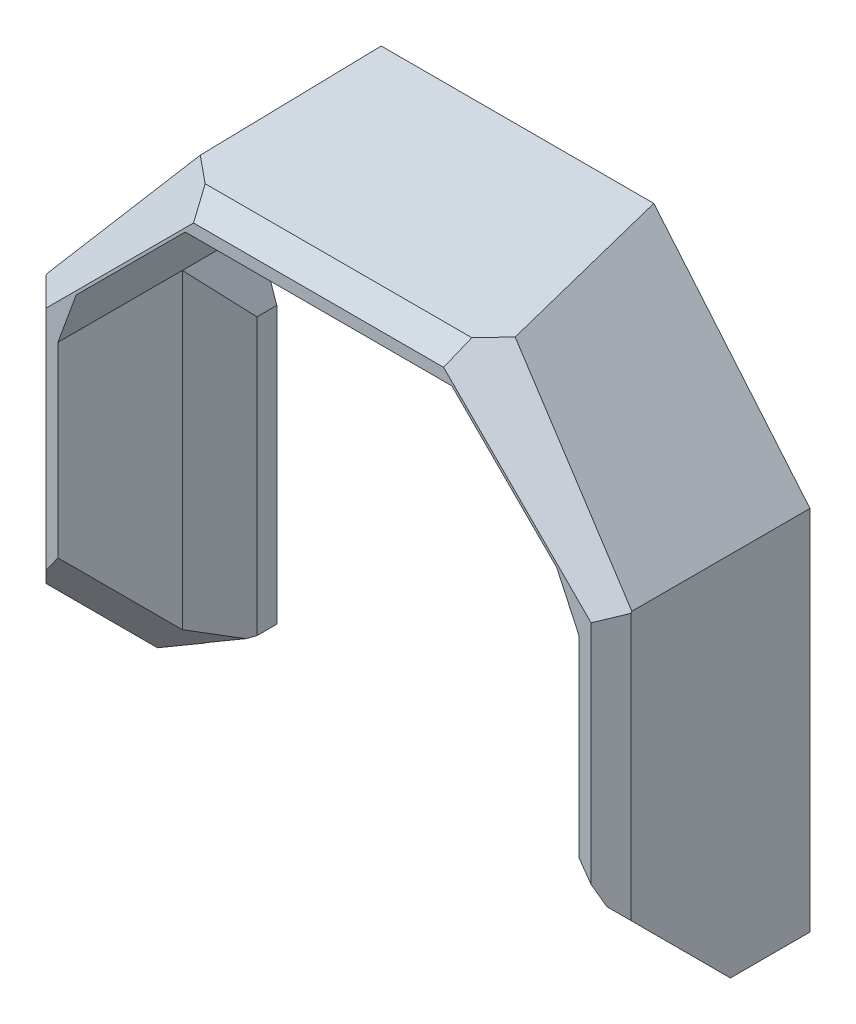
SolidWorks part; units mm, degrees
ref_plane "Спереди" through (0, 0, 0) normal (0, 0, 1) x (1, 0, 0)
ref_plane "Сверху" through (0, 0, 0) normal (0, 1, 0) x (1, 0, 0)
ref_plane "Справа" through (0, 0, 0) normal (1, 0, 0) x (0, 0, -1)
sketch "Эскиз1" plane through (0, 0, 0) normal (0, 0, 1) x (1, 0, 0)
  line L1 (-219.5225, 143.3263) -> (-117.1187, 143.3263)
  line L2 (-219.5225, 143.3263) -> (-219.5225, 57.8985)
  line L3 (-219.5225, 57.8985) -> (-117.1187, 57.8985)
  line L4 (-117.1187, 143.3263) -> (-117.1187, 57.8985)
sketch "Эскиз2" plane through (0, 0, 0) normal (0, 0, 1) x (1, 0, 0)
  line L12 (-163.3228, 250.3915) -> (-163.3228, -14.5346) construction
  line L14 (-228.8228, 61.4013) -> (-228.8228, 153.4013)
  line L15 (-228.8228, 153.4013) -> (-196.8228, 185.4013)
  line L16 (-196.8228, 185.4013) -> (-129.8228, 185.4013)
  line L17 (-129.8228, 185.4013) -> (-97.8228, 153.4013)
  line L18 (-97.8228, 153.4013) -> (-97.8228, 61.5309)
  line L19 (-252.6709, 153.4013) -> (-72.6741, 153.4013) construction
  line L20 (-97.8228, 61.5309) -> (-89.8228, 61.5309)
  line L21 (-89.8228, 61.5309) -> (-89.8228, 153.4013)
  line L22 (-89.8228, 153.4013) -> (-129.8228, 193.4013)
  line L23 (-129.8228, 193.4013) -> (-196.8228, 193.4013)
  line L24 (-196.8228, 193.4013) -> (-236.8228, 153.4013)
  line L25 (-236.8228, 153.4013) -> (-236.8228, 61.4013)
  line L26 (-236.8228, 61.4013) -> (-228.8228, 61.4013)
  line L27 (-196.8228, 216.9367) -> (-196.8228, 161.6417) construction
  line L28 (-129.8228, 216.9367) -> (-129.8228, 161.6417) construction
  point P5 (-163.3228, 185.4013)
  point P19 (0, 0)
  point P22 (0, 0)
  point P25 (0, 0)
  point P26 (0, 0)
  dimension "D1" = 135
  dimension "D2" = 135
  dimension "D3" = 67
  dimension "D4" = 92
  dimension "D5" = 32
  dimension "D6" = 8
extrude "Бобышка-Вытянуть2" add sketch "Эскиз2" along normal blind 50
chamfer "Фаска1" distance 30 angle 45 2 edges at (-232.8228, 61.4013, 50) (-93.8228, 61.5309, 50)
chamfer "Фаска2" distance 5 angle 45 5 edges at (-236.8228, 122.4013, 50) (-216.8228, 173.4013, 50) (-89.8228, 122.4661, 50) (-109.8228, 173.4013, 50) (-163.3228, 193.4013, 50)
chamfer "Фаска3" distance 5 angle 45 2 edges at (-97.8228, 76.5309, 35) (-228.8228, 76.4013, 35)
ref_plane "Плоскость4" through (-129.8228, 0, 0) normal (1, 0, 0) x (0, 0, -1)
sketch "Эскиз3" plane through (-129.8228, 0, 0) normal (1, 0, 0) x (0, 0, -1)
  line L0 (-45, 193.4013) -> (0, 193.4013)
  line L1 (0, 193.4013) -> (0, 200.5043)
  line L2 (0, 260.3915) -> (0, -1249.6085) construction
  line L3 (0, 200.5043) -> (-45, 193.4013)
extrude "Бобышка-Вытянуть3" add sketch "Эскиз3" against normal up to vertex (67 mm away) up to point (-196.8228, 193.4013, 0)
chamfer "Фаска6" distance 8 angle 20 2 edges at (-97.8228, 153.4013, 25) (-228.8228, 153.4013, 25) first distance on face at (-113.8228, 169.4013, 25) first distance on face at (-228.8228, 105.6155, 22.5858)
chamfer "Фаска7" distance 8 angle 40 1 edges at (-196.8228, 193.4013, 22.5) first distance on face at (-196.8228, 195.769, 15)
chamfer "Фаска8" distance 8 angle 40 1 edges at (-129.8228, 193.4013, 22.5) first distance on face at (-129.8228, 195.769, 15)
ref_plane "Плоскость5" through (0, 0, 0) normal (0, 0, -1) x (-1, 0, 0)
sketch "Эскиз4" plane through (0, 0, 0) normal (0, 0, -1) x (-1, 0, 0)
  line L0 (97.8228, 146.927) -> (102.8228, 130.927)
  line L2 (97.8228, 146.927) -> (97.8228, 61.5309)
  line L3 (97.8228, 61.5309) -> (102.8228, 61.5309)
  line L4 (102.8228, 130.927) -> (102.8228, 61.5309)
  line L6 (228.8228, 145.4013) -> (228.8228, 61.5309)
  line L7 (228.8228, 61.5309) -> (223.8228, 61.5309)
  line L8 (223.8228, 130.927) -> (223.8228, 61.5309)
  line L9 (77.7191, 130.927) -> (254.7535, 130.927) construction
  line L10 (228.8228, 145.4013) -> (223.8228, 130.927)
  dimension "D1" = 5
  dimension "D2" = 5
  dimension "D3" = 16
extrude "Бобышка-Вытянуть4" add sketch "Эскиз4" against normal blind 5
chamfer "Фаска9" distance 5 angle 70 2 edges at (-97.8228, 104.229, 5) (-228.8228, 103.4661, 5) first distance on face at (-100.3228, 100.229, 5) first distance on face at (-226.3228, 99.8475, 5)
sketch "Эскиз5" plane through (0, 0, 0) normal (0, 0, -1) x (-1, 0, 0)
  line L0 (163.3228, 200.5043) -> (163.3228, 185.4013) construction
  line L1 (197.5755, 200.5043) -> (129.0701, 200.5043) construction
  line L2 (89.8228, 86.5309) -> (102.8228, 86.5309) construction
  line L4 (196.8228, 185.4013) -> (129.8228, 185.4013) construction
  line L5 (89.8228, 61.5309) -> (89.8228, 153.7312) construction
  line L6 (102.8228, 61.5309) -> (102.8228, 130.927) construction
  line L7 (223.8228, 86.5309) -> (236.8228, 86.5309) construction
  line L8 (223.8228, 130.927) -> (223.8228, 61.5309) construction
  line L9 (236.8228, 153.7312) -> (236.8228, 61.4013) construction
  line L10 (102.8228, 61.5309) -> (89.8228, 61.5309) construction
  circle A0 centre (96.3228, 86.5309) radius 1.1
  circle A1 centre (230.3228, 86.5309) radius 1.1
  circle A2 centre (163.3228, 192.9528) radius 1.1
  dimension "D2" = 2.2
  dimension "D3" = 2.2
  dimension "D4" = 2.2
  dimension "D1" = 25
extrude "Вырез-Вытянуть1" cut sketch "Эскиз5" against normal blind 20
equation "\"D3@Эскиз5\"=\"D2@Эскиз5\""
equation "\"D4@Эскиз5\"=\"D2@Эскиз5\""
